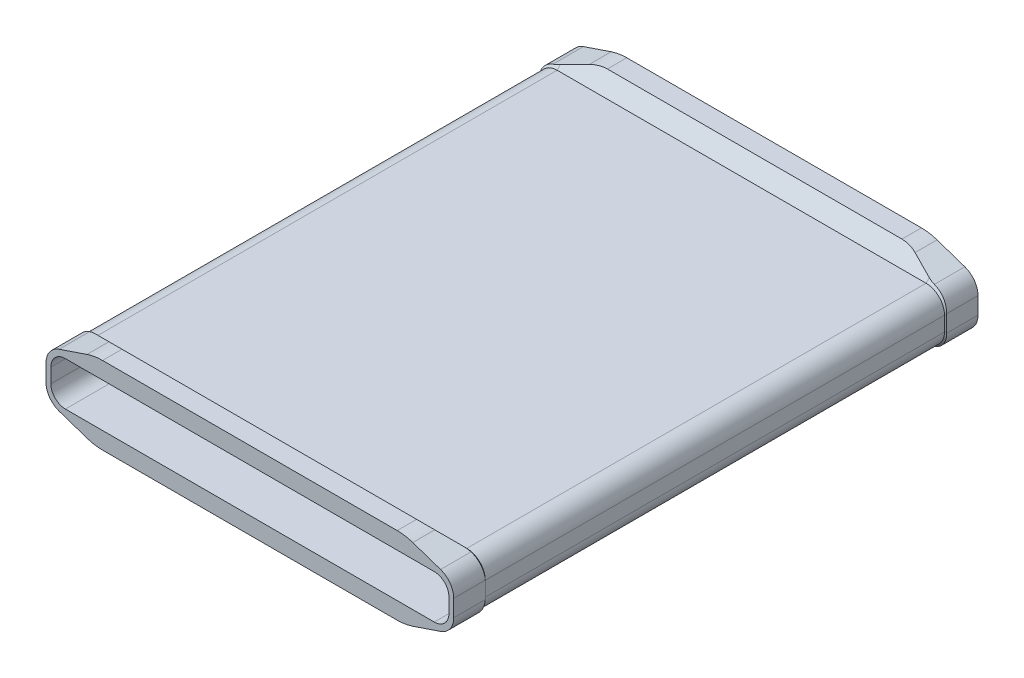
SolidWorks part; units mm, degrees
material "ABS"
ref_plane "Front Plane" through (0, 0, 0) normal (0, 0, 1) x (1, 0, 0)
ref_plane "Top Plane" through (0, 0, 0) normal (0, 1, 0) x (1, 0, 0)
ref_plane "Right Plane" through (0, 0, 0) normal (1, 0, 0) x (0, 0, -1)
sketch "Sketch1" plane through (0, 0, 0) normal (0, 0, 1) x (1, 0, 0)
  line L0 (-21, 4) -> (21, -4) construction
  line L1 (-21, -4) -> (21, -4)
  line L2 (-21, -4) -> (-21, 4)
  line L3 (-21, 4) -> (21, 4)
  line L4 (21, -4) -> (21, 4)
  line L5 (21, 4) -> (-21, -4) construction
  dimension "D1" = 42
  dimension "D2" = 8
extrude "Boss-Extrude1" add sketch "Sketch1" along normal blind 54
sketch "Sketch5" plane through (0, 0, 54) normal (0, 0, 1) x (1, 0, 0)
  line L0 (-21, 4) -> (-21, 2.3022)
  line L1 (-21, 4) -> (-21, -4) construction
  line L2 (-21, 2.3022) -> (-16, 4)
  line L3 (21, 4) -> (-21, 4) construction
  line L4 (-16, 4) -> (-21, 4)
  circle A0 centre (-20.5, 3) radius 0.5 construction
  dimension "D1" = 1
  dimension "D2" = 1
  dimension "D3" = 5
extrude "Cut-Extrude5" cut sketch "Sketch5" against normal up to next
mirror "Mirror1" about plane through (0, 0, 0) normal (0, 1, 0) of "Cut-Extrude5"
mirror "Mirror2" about plane through (0, 0, 0) normal (1, 0, 0) of "Mirror1"
sketch "Sketch2" plane through (0, 0, 54) normal (0, 0, 1) x (1, 0, 0)
  line L1 (-19, -2.25) -> (19, -2.25)
  line L2 (-20.5, -0.75) -> (-20.5, 0.75)
  line L3 (-19, 2.25) -> (19, 2.25)
  line L4 (20.5, -0.75) -> (20.5, 0.75)
  line L5 (-20.5, -2.25) -> (20.5, 2.25) construction
  line L6 (-20.5, 2.25) -> (20.5, -2.25) construction
  arc A0 (19, 2.25) -> (20.5, 0.75) centre (19, 0.75) cw
  arc A1 (19, -2.25) -> (20.5, -0.75) centre (19, -0.75) ccw
  arc A2 (-20.5, 0.75) -> (-19, 2.25) centre (-19, 0.75) cw
  arc A3 (-19, -2.25) -> (-20.5, -0.75) centre (-19, -0.75) cw
  point P0 (0, 0)
  dimension "D3" = 1.5
  dimension "D1" = 4.5
  dimension "D2" = 41
extrude "Cut-Extrude2" cut sketch "Sketch2" against normal up to next
sketch "Sketch3" plane through (0, 0, 54) normal (0, 0, 1) x (1, 0, 0)
  line L30 (20.9, -0.75) -> (20.9, 0.75)
  line L31 (-19, -2.65) -> (19, -2.65)
  line L32 (-20.9, 0.75) -> (-20.9, -0.75)
  line L33 (19, 2.65) -> (-19, 2.65)
  line L34 (20.9, -0.75) -> (20.9, 0.75)
  line L35 (-19, -2.65) -> (19, -2.65)
  line L36 (-20.9, 0.75) -> (-20.9, -0.75)
  line L37 (19, 2.65) -> (-19, 2.65)
  arc A24 (20.9, 0.75) -> (19, 2.65) centre (19, 0.75) ccw
  arc A25 (19, -2.65) -> (20.9, -0.75) centre (19, -0.75) ccw
  arc A26 (-20.9, -0.75) -> (-19, -2.65) centre (-19, -0.75) ccw
  arc A27 (-19, 2.65) -> (-20.9, 0.75) centre (-19, 0.75) ccw
  arc A28 (20.9, 0.75) -> (19, 2.65) centre (19, 0.75) ccw
  arc A29 (19, -2.65) -> (20.9, -0.75) centre (19, -0.75) ccw
  arc A30 (-20.9, -0.75) -> (-19, -2.65) centre (-19, -0.75) ccw
  arc A31 (-19, 2.65) -> (-20.9, 0.75) centre (-19, 0.75) ccw
  dimension "D1" = 0.4
extrude "Cut-Extrude3" cut sketch "Sketch3" against normal offset from surface (50 mm away) 2 from offset 2 flip side to cut up to face at (0, 0, 0) offset against normal yes
fillet "Fillet1" radius 2 8 edges at (21, 2.3022, 1) (21, -2.3022, 1) (-21, -2.3022, 1) (-21, 2.3022, 1) (-21, 2.3022, 53) (-21, -2.3022, 53) (21, -2.3022, 53) (21, 2.3022, 53)
fillet "Fillet2" radius 5 8 edges at (16, -4, 1) (-16, -4, 1) (16, -4, 53) (-16, -4, 53) (16, 4, 53) (-16, 4, 53) (16, 4, 1) (-16, 4, 1)
chamfer "Chamfer1" distance 1.35 angle 45 16 edges at (0, -2.65, 2) (20.3435, -2.0935, 2) (-20.3435, -2.0935, 2) (20.9, 0, 2) (-20.9, 0, 2) (20.3435, 2.0935, 2) (-20.3435, 2.0935, 2) (0, 2.65, 2) (0, -2.65, 52) (20.3435, -2.0935, 52) (-20.3435, -2.0935, 52) (20.9, 0, 52) (-20.9, 0, 52) (20.3435, 2.0935, 52) (-20.3435, 2.0935, 52) (0, 2.65, 52)
